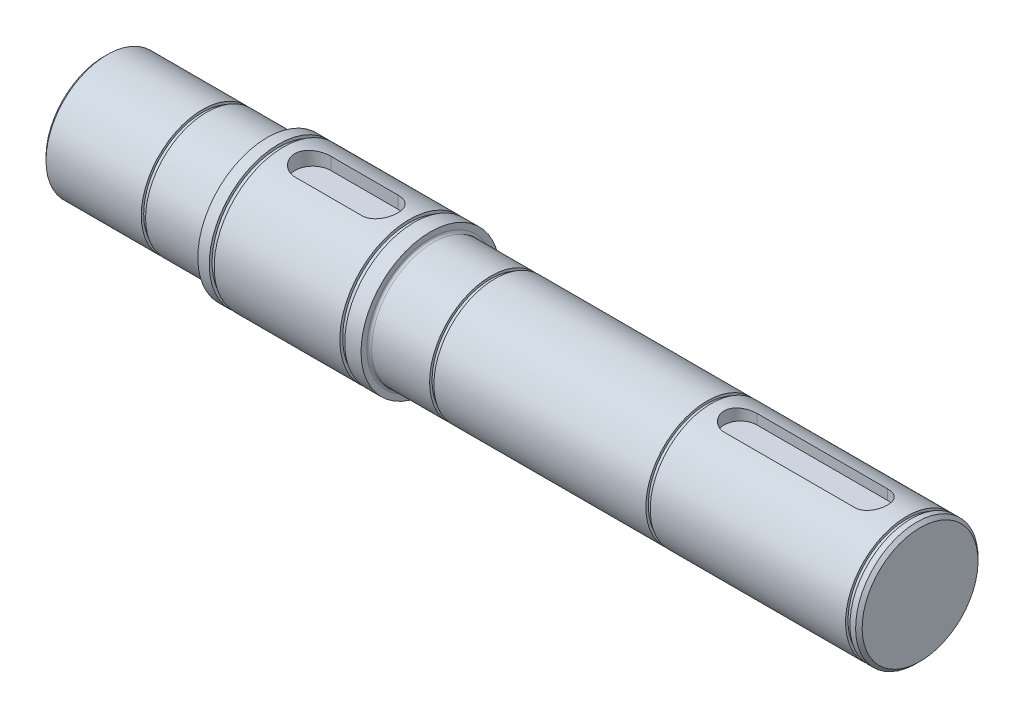
SolidWorks part; units mm, degrees
ref_plane "Front" through (0, 0, 0) normal (0, 0, 1) x (1, 0, 0)
ref_plane "Top" through (0, 0, 0) normal (0, 1, 0) x (1, 0, 0)
ref_plane "Right" through (0, 0, 0) normal (1, 0, 0) x (0, 0, -1)
sketch "Esquisse1" plane through (0, 0, 0) normal (0, 0, 1) x (1, 0, 0)
  line L0 (0, 0) -> (0, 37.5)
  line L1 (0, 37.5) -> (98.5, 37.5)
  line L3 (100, 42.5) -> (200, 42.5)
  line L5 (201.5, 37.5) -> (500, 37.5)
  line L6 (500, 37.5) -> (500, 0)
  line L7 (500, 0) -> (0, 0)
  line L8 (100, 42.5) -> (100, 39)
  line L9 (200, 42.5) -> (200, 39)
  arc A2 (200, 39) -> (201.5, 37.5) centre (201.5, 39) ccw
  arc A3 (100, 39) -> (98.5, 37.5) centre (98.5, 39) cw
  dimension "D4" = 1.5
  dimension "D1" = 37.5
  dimension "D2" = 100
  dimension "D3" = 500
  dimension "D5" = 42.5
  dimension "D7" = 100
revolve "Révolution1" add sketch "Esquisse1" angle 360 about L7
ref_plane "Plan1" through (110, 0, 0) normal (1, 0, 0) x (0, 0, -1)
ref_plane "Plan2" through (190, 0, 0) normal (1, 0, 0) x (0, 0, -1)
sketch "Esquisse2" plane through (110, 0, 0) normal (1, 0, 0) x (0, 0, -1)
  circle A2 centre (0, 0) radius 42.5
  circle A3 centre (0, 0) radius 40.75
  dimension "D1" = 1.75
extrude "Enlèv. mat.-Extru.1" cut sketch "Esquisse2" against normal blind 3
sketch "Esquisse3" plane through (190, 0, 0) normal (1, 0, 0) x (0, 0, -1)
  circle A1 centre (0, 0) radius 42.5
  circle A2 centre (0, 0) radius 40.75
  dimension "D1" = 1.75
extrude "Enlèv. mat.-Extru.2" cut sketch "Esquisse3" against normal blind 3
ref_plane "Plan3" through (0, 42.5, 0) normal (0, 1, 0) x (1, 0, 0)
sketch "Esquisse4" plane through (0, 42.5, 0) normal (0, 1, 0) x (1, 0, 0)
  line L0 (148.5, 42.5) -> (148.5, 0) construction
  line L1 (187, 42.5) -> (110, 42.5) construction
  line L2 (128, 0) -> (169, 0) construction
  line L3 (128, 11) -> (169, 11)
  line L4 (128, -11) -> (169, -11)
  arc A0 (128, 11) -> (128, -11) centre (128, 0) ccw
  arc A1 (169, -11) -> (169, 11) centre (169, 0) ccw
  point P6 (148.5, 0)
  dimension "D2" = 11
  dimension "D1" = 41
extrude "Enlèv. mat.-Extru.3" cut sketch "Esquisse4" against normal blind 9
ref_plane "Plan4" through (0, 37.5, 0) normal (0, 1, 0) x (1, 0, 0)
sketch "Esquisse5" plane through (0, 37.5, 0) normal (0, 1, 0) x (1, 0, 0)
  line L0 (500, 0) -> (430, 0) construction
  line L1 (500, -37.5) -> (500, 37.5) construction
  line L2 (470, 0) -> (390, 0) construction
  line L3 (470, -10) -> (390, -10)
  line L4 (470, 10) -> (390, 10)
  arc A0 (470, -10) -> (470, 10) centre (470, 0) ccw
  arc A1 (390, 10) -> (390, -10) centre (390, 0) ccw
  point P7 (430, 0)
  dimension "D2" = 10
  dimension "D1" = 70
  dimension "D3" = 80
extrude "Enlèv. mat.-Extru.4" cut sketch "Esquisse5" against normal blind 7.5
chamfer "Chanfrein1" distance 2 angle 45 2 edges at (500, 37.5, 0) (0, 37.5, 0)
ref_plane "Plan5" through (494.5, 0, 0) normal (1, 0, 0) x (0, 0, -1)
sketch "Esquisse6" plane through (494.5, 0, 0) normal (1, 0, 0) x (0, 0, -1)
  circle A0 centre (0, 0) radius 37.5 construction
  circle A1 centre (0, 0) radius 37.5
  circle A2 centre (0, 0) radius 36
  dimension "D1" = 1.5
extrude "Enlèv. mat.-Extru.5" cut sketch "Esquisse6" against normal blind 2.65
ref_plane "Plan6" through (60.35, 0, 0) normal (-1, 0, 0) x (0, 0, 1)
sketch "Esquisse7" plane through (60.35, 0, 0) normal (-1, 0, 0) x (0, 0, 1)
  circle A0 centre (0, 0) radius 37.5 construction
  circle A1 centre (0, 0) radius 37.5
  circle A2 centre (0, 0) radius 36
  dimension "D1" = 1.5
extrude "Enlèv. mat.-Extru.6" cut sketch "Esquisse7" against normal blind 2.65
ref_plane "Plan8" through (239.65, 0, 0) normal (-1, 0, 0) x (0, 0, 1)
sketch "Esquisse8" plane through (239.65, 0, 0) normal (-1, 0, 0) x (0, 0, 1)
  circle A0 centre (0, 0) radius 37.5 construction
  circle A1 centre (0, 0) radius 37.5
  circle A2 centre (0, 0) radius 36
  dimension "D1" = 1.5
extrude "Enlèv. mat.-Extru.7" cut sketch "Esquisse8" along normal blind 2.65
ref_plane "Plan9" through (369.5, 0, 0) normal (1, 0, 0) x (0, 0, -1)
sketch "Esquisse10" plane through (369.5, 0, 0) normal (1, 0, 0) x (0, 0, -1)
  circle A1 centre (0, 0) radius 37.5
  circle A2 centre (0, 0) radius 36
  dimension "D1" = 1.5
extrude "Enlèv. mat.-Extru.11" cut sketch "Esquisse10" along normal blind 2.65
